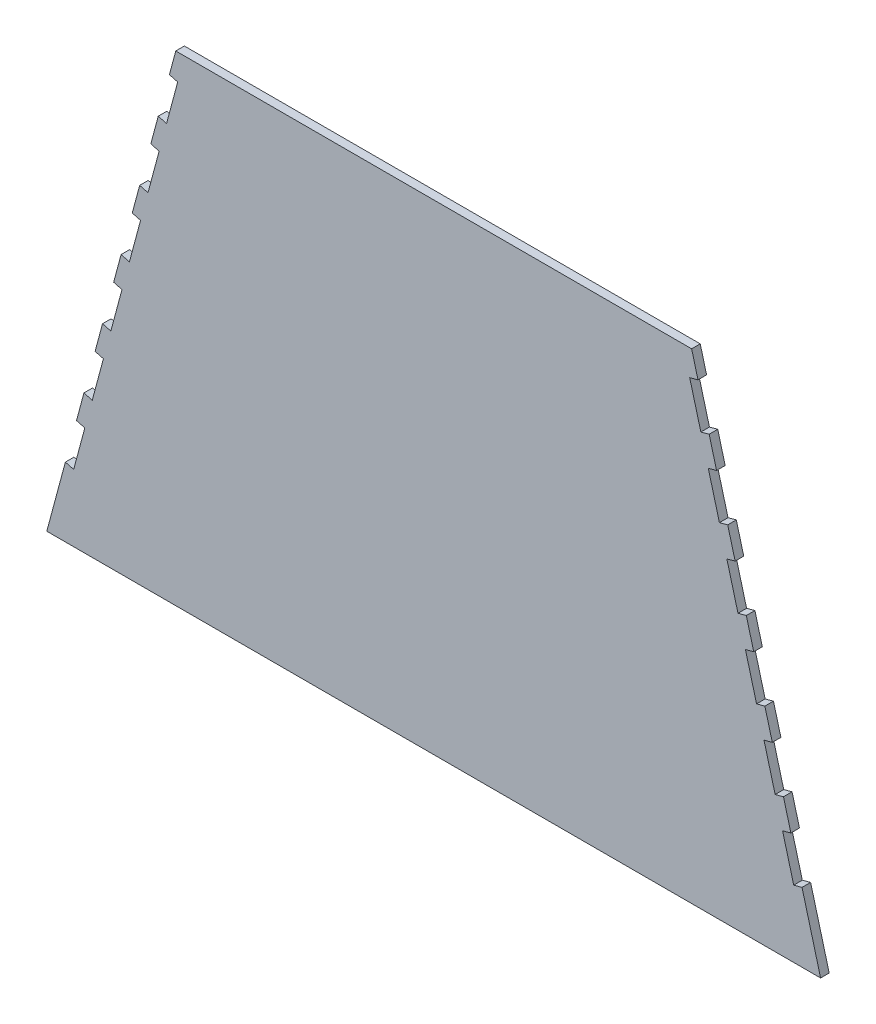
SolidWorks part; units mm, degrees
ref_plane "Front Plane" through (0, 0, 0) normal (0, 0, 1) x (1, 0, 0)
ref_plane "Top Plane" through (0, 0, 0) normal (0, 1, 0) x (1, 0, 0)
ref_plane "Right Plane" through (0, 0, 0) normal (1, 0, 0) x (0, 0, -1)
sketch "Sketch1" plane through (0, 0, 0) normal (0, 0, 1) x (1, 0, 0)
  line L0 (-135, -83.8153) -> (135, -83.8153)
  line L1 (135, -83.8153) -> (90, 83.8153)
  line L2 (90, 83.8153) -> (-90, 83.8153)
  line L3 (-90, 83.8153) -> (-135, -83.8153)
  line L7 (0, 83.8153) -> (0, -83.8153) construction
  dimension "D1" = 180
  dimension "D2" = 173.5655
  dimension "D3" = 173.5655
  dimension "D4" = 270
extrude "Boss-Extrude1" add sketch "Sketch1" along normal blind 3
sketch "Sketch2" plane through (0, 0, 3) normal (0, 0, 1) x (1, 0, 0)
  line L0 (-128.5183, -59.6701) -> (-125.6209, -60.4479)
  line L1 (-90, 83.8153) -> (-135, -83.8153) construction
  line L2 (-125.6209, -60.4479) -> (-121.7319, -45.9609)
  line L3 (-121.7319, -45.9609) -> (-124.6293, -45.1831)
  line L10 (-124.6293, -45.1831) -> (-128.5183, -59.6701)
  dimension "D1" = 3
  dimension "D2" = 15
  dimension "D3" = 25
extrude "Cut-Extrude2" cut sketch "Sketch2" against normal blind 3
pattern_linear "LPattern2" count 6 spacing 25 along (0.2593, 0.9658, 0) of "Cut-Extrude2"
sketch "Sketch3" plane through (0, 0, 3) normal (0, 0, 1) x (1, 0, 0)
  line L0 (128.5183, -59.6701) -> (124.6293, -45.1831)
  line L1 (135, -83.8153) -> (90, 83.8153) construction
  line L2 (124.6293, -45.1831) -> (121.7319, -45.9609)
  line L3 (121.7319, -45.9609) -> (125.6209, -60.4479)
  line L4 (125.6209, -60.4479) -> (128.5183, -59.6701)
  dimension "D1" = 15
  dimension "D2" = 3
  dimension "D3" = 25
extrude "Cut-Extrude3" cut sketch "Sketch3" against normal blind 3
pattern_linear "LPattern3" count 6 spacing 25 along (-0.2593, 0.9658, 0) of "Cut-Extrude3"
